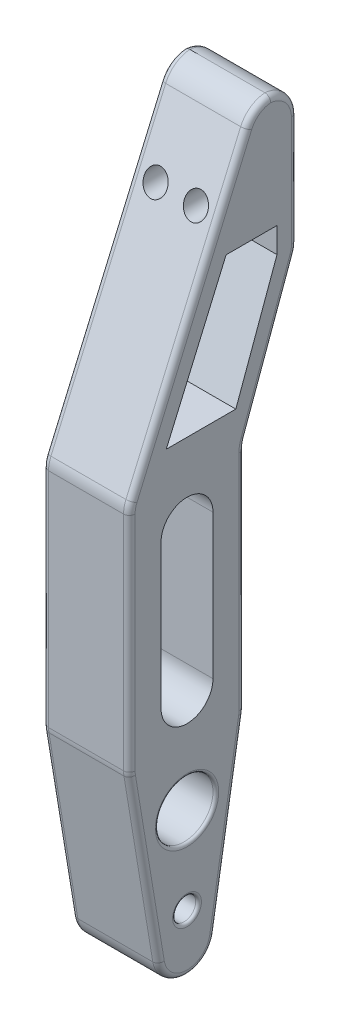
SolidWorks part; units mm, degrees
material "6061-T6 (SS)"
ref_plane "Front Plane" through (0, 0, 0) normal (0, 0, 1) x (1, 0, 0)
ref_plane "Top Plane" through (0, 0, 0) normal (0, 1, 0) x (1, 0, 0)
ref_plane "Right Plane" through (0, 0, 0) normal (1, 0, 0) x (0, 0, -1)
sketch "Sketch2" plane through (0, 0, 0) normal (1, 0, 0) x (0, 0, -1)
  line L0 (0, 207.1878) -> (0, -10) construction
  line L1 (-136.5118, 60) -> (124.7741, 60) construction
  line L2 (-20, 60) -> (-9.8675, -1.6225)
  line L3 (20, 60) -> (20, 140)
  line L4 (20, 140) -> (38.1985, 190)
  line L5 (-20, 60) -> (-20, 140)
  line L6 (38.1985, 190) -> (38.1985, 240)
  line L7 (38.1985, 240) -> (23.1985, 240)
  line L8 (20, 60) -> (9.8675, -1.6225)
  line L9 (0, 140) -> (20, 140) construction
  line L10 (-116.1864, -1.6225) -> (106.5888, -1.6225) construction
  line L11 (23.1985, 240) -> (-20, 140)
  line L12 (20, 140) -> (233.1792, 140) construction
  line L13 (0, 140) -> (0, 60) construction
  line L14 (0, 125) -> (0, 75) construction
  line L15 (9, 125) -> (9, 75)
  line L16 (-9, 125) -> (-9, 75)
  line L17 (16.9184, 152) -> (31.1985, 191.2343)
  line L18 (13.5443, 200) -> (31.1985, 200)
  line L19 (31.1985, 200) -> (31.1985, 191.2343)
  line L20 (13.5443, 200) -> (-7.191, 152)
  line L21 (-7.191, 152) -> (16.9184, 152)
  arc A0 (-9.8675, -1.6225) -> (9.8675, -1.6225) centre (0, 0) ccw
  circle A1 centre (0, 10) radius 4
  circle A2 centre (0, 40) radius 10
  arc A3 (9, 125) -> (-9, 125) centre (0, 125) ccw
  arc A4 (-9, 75) -> (9, 75) centre (0, 75) ccw
  point P14 (0, 100)
  point P25 (0, 100)
  dimension "D2" = 70
  dimension "D5" = 20
  dimension "D6" = 20
  dimension "D10" = 20
  dimension "D11" = 35
  dimension "D4" = 50
  dimension "D13" = 50
  dimension "D1" = 20
  dimension "D12" = 15
  dimension "D3" = 80
  dimension "D7" = 70
  dimension "D8" = 50
  dimension "D9" = 15
  dimension "D14" = 18
  dimension "D15" = 7
  dimension "D16" = 7
  dimension "D17" = 7
  dimension "D18" = 40
  dimension "D19" = 12
  dimension "D20" = 30
extrude "Boss-Extrude1" add sketch "Sketch2" along normal blind 30
fillet "Fillet1" radius 10 7 edges at (15, 190, -38.1985) (15, 140, -20) (15, 60, -20) (15, 60, 20) (15, 240, -23.1985) (15, 240, -38.1985) (15, 140, 20)
sketch "Sketch3" plane through (0, 0, -38.1985) normal (0, 0, -1) x (-1, 0, 0)
  line L0 (0, 230) -> (-30, 230) construction
  circle A0 centre (-8, 212) radius 4
  circle A1 centre (-22, 212) radius 4
  point P6 (-15, 230)
  dimension "D1" = 7
  dimension "D2" = 7
  dimension "D3" = 18
  dimension "D4" = 18
extrude "Cut-Extrude1" cut sketch "Sketch3" against normal blind 37
fillet "Fillet2" radius 2 30 edges at (0, 238.1336, -23.9543) (0, 187.9319, -0.7058) (0, 139.9572, 19.7929) (0, 99.3745, 20) (0, 60.0027, 19.9668) (0, 28.7858, 14.8675) (0, -10, 0) (0, 28.7858, -14.8675) (0, 60.0027, -19.9668) (0, 236.7872, -35.5424) (0, 210.8816, -38.1985) (0, 190.0268, -38.0466) (0, 165, -29.0993) (0, 139.9732, -20.1519) (30, 238.1336, -23.9543) (30, 187.9319, -0.7058) (30, 139.9572, 19.7929) (30, 99.3745, 20) (30, 60.0027, 19.9668) (30, 28.7858, 14.8675) (30, -10, 0) (30, 28.7858, -14.8675) (30, 60.0027, -19.9668) (30, 99.5267, -20) (30, 139.9732, -20.1519) (30, 236.7872, -35.5424) (30, 210.8816, -38.1985) (30, 190.0268, -38.0466) (0, 99.5267, -20) (30, 165, -29.0993)
fillet "Fillet3" radius 1 4 edges at (0, 40, -10) (0, 10, -4) (30, 40, -10) (30, 10, -4)
